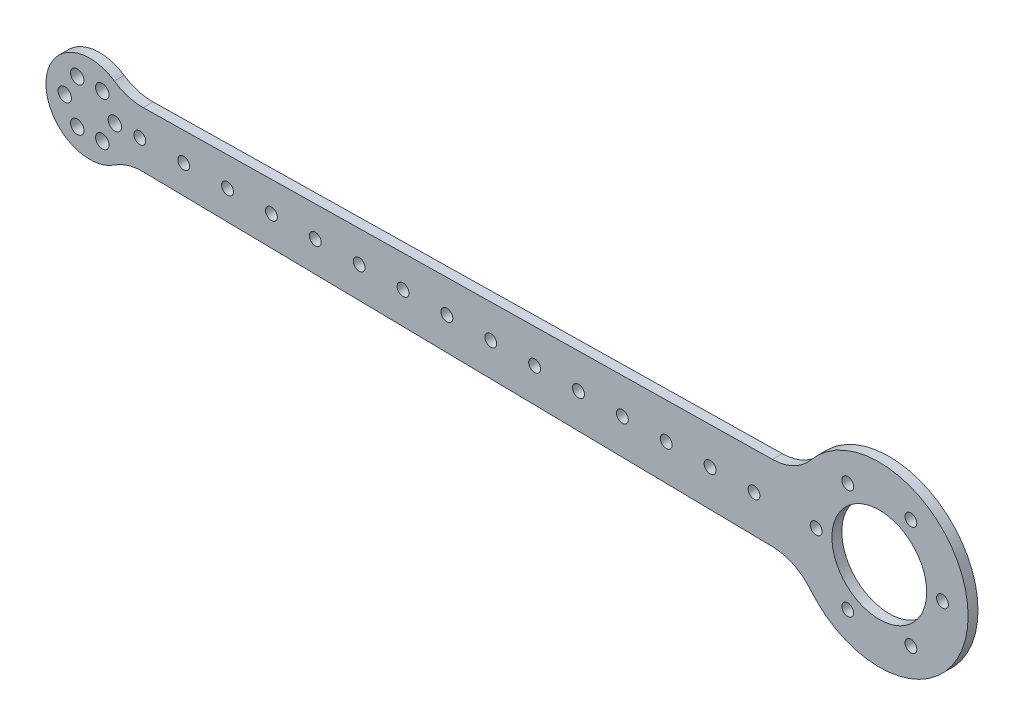
SolidWorks part; units mm, degrees
material "Hexcel AS4C (3000 Filaments)"
ref_plane "Front Plane" through (0, 0, 0) normal (0, 0, 1) x (1, 0, 0)
ref_plane "Top Plane" through (0, 0, 0) normal (0, 1, 0) x (1, 0, 0)
ref_plane "Right Plane" through (0, 0, 0) normal (1, 0, 0) x (0, 0, -1)
sketch "Sketch1" plane through (0, 0, 0) normal (0, 0, 1) x (1, 0, 0)
  line L0 (-100, 0) -> (100, 0) construction
  line L1 (-88.9892, 1.5) -> (77.8859, 4.1495)
  line L2 (-91.3398, 6.9634) -> (79.6881, 9.6788)
  line L3 (-88.9892, -1.5) -> (77.8859, -4.1495)
  line L4 (-91.3398, -6.9634) -> (79.6881, -9.6788)
  line L5 (-100, 0) -> (-100.1083, -6.8242) construction
  line L6 (-100.1083, -6.8242) -> (-91.3398, -6.9634) construction
  line L7 (-91.3398, 6.9634) -> (-100.1083, 6.8242) construction
  line L8 (-100.1083, 6.8242) -> (-100, 0) construction
  line L9 (-88.9892, 1.5) -> (-88.9892, -1.5)
  line L10 (100, 0) -> (99.8413, -9.9987) construction
  line L11 (99.8413, -9.9987) -> (79.6881, -9.6788) construction
  line L12 (79.6881, 9.6788) -> (99.8413, 9.9987) construction
  line L13 (99.8413, 9.9987) -> (100, 0) construction
  circle A0 centre (-100, 0) radius 11.1125 construction
  circle A1 centre (100, 0) radius 22.5 construction
  arc A2 (79.6881, 9.6788) -> (79.6881, -9.6788) centre (100, 0) cw
  arc A3 (77.8859, 4.1495) -> (77.8859, -4.1495) centre (100, 0) ccw
  arc A4 (-91.3398, 6.9634) -> (-91.3398, -6.9634) centre (-100, 0) ccw
  point P4 (0, 0)
  point P23 (-88.9892, 0)
  dimension "D2" = 22.225
  dimension "D3" = 45
  dimension "D1" = 200
  dimension "D5" = 5.5
  dimension "D6" = 10
  dimension "D7" = 5.5
  dimension "D4" = 10
  dimension "D8" = 3
extrude "Boss-Extrude1" add sketch "Sketch1" along normal mid plane 2.5
fillet "Fillet1" radius 12.7 4 edges at (79.6881, 9.6788, 0) (79.6881, -9.6788, 0) (-91.3398, -6.9634, 0) (-91.3398, 6.9634, 0)
sketch "Sketch2" plane through (0, 0, 0) normal (0, 0, 1) x (1, 0, 0)
  line L8 (-88.9892, 1.5) -> (-88.9892, -1.5) construction
  line L9 (-88.9892, -1.5) -> (77.8859, -4.1495) construction
  line L10 (77.8859, 4.1495) -> (-88.9892, 1.5) construction
  line L12 (-88.9892, 1.5) -> (-88.9892, -1.5)
  line L13 (-88.9892, -1.5) -> (77.8859, -4.1495)
  line L14 (77.8859, 4.1495) -> (-88.9892, 1.5)
  arc A6 (77.8859, 4.1495) -> (77.8859, -4.1495) centre (100, 0) ccw construction
  arc A7 (77.8859, 4.1495) -> (77.8859, -4.1495) centre (100, 0) ccw
extrude "Boss-Extrude2" add sketch "Sketch2" along normal mid plane 2.5
ref_axis "Axis1" through (100, 0, 1.25) along (0, 0, -1)
ref_axis "Axis2" through (-100, 0, 1.25) along (0, 0, -1)
sketch "Sketch3" plane through (0, 0, 0) normal (0, 0, 1) x (1, 0, 0)
  circle A0 centre (100, 0) radius 12
  dimension "D1" = 24
extrude "Cut-Extrude1" cut sketch "Sketch3" against normal through all both and the other way through all
sketch "Sketch5" plane through (0, 0, 0) normal (0, 0, 1) x (1, 0, 0)
  line L0 (100, 0) -> (116, 0) construction
  circle A0 centre (116, 0) radius 1.5
  dimension "D2" = 3
  dimension "D1" = 16
extrude "Cut-Extrude2" cut sketch "Sketch5" against normal through all both and the other way through all
pattern_circular "CirPattern1" count 6 over 360 about axis through (100, 0, 1.25) along (0, 0, -1) of "Cut-Extrude2"
sketch "Sketch6" plane through (0, 0, 1.25) normal (0, 0, 1) x (1, 0, 0)
  line L0 (100, 0) -> (68.25, 0) construction
  line L1 (-100, 0) -> (-31.7625, 0) construction
  circle A0 centre (68.25, 0) radius 1.5
  circle A1 centre (57.1375, 0) radius 1.5
  circle A2 centre (46.025, 0) radius 1.5
  circle A3 centre (34.9125, 0) radius 1.5
  circle A4 centre (23.8, 0) radius 1.5
  circle A5 centre (12.6875, 0) radius 1.5
  circle A6 centre (1.575, 0) radius 1.5
  circle A7 centre (-9.5375, 0) radius 1.5
  circle A8 centre (-20.65, 0) radius 1.5
  circle A9 centre (-31.7625, 0) radius 1.5
  circle A10 centre (-42.875, 0) radius 1.5
  circle A11 centre (-53.9875, 0) radius 1.5
  circle A12 centre (-65.1, 0) radius 1.5
  circle A13 centre (-76.2125, 0) radius 1.5
  circle A14 centre (-87.325, 0) radius 1.5
  dimension "D1" = 3
  dimension "D2" = 31.75
  dimension "D4" = 11.1125
  dimension "D3" = 15
extrude "Cut-Extrude3" cut sketch "Sketch6" against normal through all both and the other way through all
sketch "Sketch8" plane through (0, 0, 0) normal (0, 0, 1) x (1, 0, 0)
  line L1 (-115, -25.4) -> (-85, -25.4)
  line L2 (-115, -25.4) -> (-115, 25.4)
  line L3 (-115, 25.4) -> (-85, 25.4)
  line L4 (-85, -25.4) -> (-85, 25.4)
  line L5 (-115, -25.4) -> (-85, 25.4) construction
  line L6 (-115, 25.4) -> (-85, -25.4) construction
  point P0 (-100, 0)
  dimension "D1" = 15
  dimension "D2" = 50.8
extrude "Cut-Extrude4" [suppressed] cut sketch "Sketch8" against normal through all both and the other way through all
fillet "Fillet2" [suppressed] radius 2.3813
sketch "Sketch10" [suppressed] plane through (0, 0, 1.25) normal (0, 0, 1) x (1, 0, 0)
  line L0 (-100, 0) -> (-81.825, 0) construction
  line L1 (-85, -4.7688) -> (-85, 4.7688) construction
  line L2 (-81.825, -4) -> (-69.125, -4) construction
  line L3 (-81.825, -4) -> (-81.825, 4) construction
  line L4 (-81.825, 4) -> (-69.125, 4) construction
  line L5 (-69.125, -4) -> (-69.125, 4) construction
  circle A0 centre (-81.825, 4) radius 1.5
  circle A1 centre (-69.125, 4) radius 1.5
  circle A2 centre (-69.125, -4) radius 1.5
  circle A3 centre (-81.825, -4) radius 1.5
  point P8 (-81.825, 0)
  dimension "D4" = 3
  dimension "D1" = 3.175
  dimension "D2" = 12.7
  dimension "D3" = 8
extrude "Cut-Extrude5" [suppressed] cut sketch "Sketch10" against normal through all both and the other way through all
sketch "Sketch11" plane through (0, 0, 0) normal (0, 0, -1) x (-1, 0, 0)
  line L0 (93.65, 0) -> (100, 0) construction
  point P4 (93.65, 0)
  dimension "D2" = 6.35
hole_wizard "M3 Clearance Hole1" positions "Sketch12" profile "Sketch13" hole size "M3" standard "ANSI Metric" end condition up to next
sketch "Sketch12" plane through (0, 0, -1.25) normal (0, 0, -1) x (-1, 0, 0)
  point P0 (93.65, 0)
sketch "Sketch13" plane through (-93.65, 0, -1.25) normal (1, 0, 0) x (0, 1, 0)
  line L0 (0, 0) -> (0, 2.501)
  line L1 (0, 2.501) -> (1.7, 2.501)
  line L2 (1.7, 2.501) -> (1.7, 0)
  line L5 (1.7, 0) -> (0, 0)
  line L11 (0, -6.35) -> (0, 107.95) construction
  dimension "Thru Hole Dia." = 3.4
  dimension "Thru Hole Depth" = 2.501
pattern_circular "CirPattern3" count 6 over 360 about axis through (-100, 0, 1.25) along (0, 0, -1) of "M3 Clearance Hole1" reverse direction yes
equation "\"length\"= 200mm"
equation "\"D1@Sketch1\"=\"length\""
equation "\"Flange_Pulle\"= 45mm"
equation "\"D3@Sketch1\"=\"Flange_Pulle\""
equation "\"C_Upper\"= 10mm"
equation "\"Upper_Thickness\"= 5.5mm"
equation "\"D5@Sketch1\"=\"Upper_Thickness\""
equation "\"C_Lower\"= 10mm"
equation "\"D6@Sketch1\"=\"C_Lower\""
equation "\"Lower_Thickness\"= 5.5mm"
equation "\"D7@Sketch1\"=\"Lower_Thickness\""
equation "\"Foot_Diameter\"=0.875"
equation "\"D2@Sketch1\"=\"Foot_Diameter\""
equation "\"Thicknes\"= 2.5mm"
equation "\"D1@Boss-Extrude1\"=\"Thicknes\""
equation "\"D1@Boss-Extrude2\"=\"Thicknes\""
equation "\"D4@Sketch1\"=\"C_Upper\""
equation "\"m3_clearance\"= 3mm"
equation "\"screw_center_offset\"= 16mm"
equation "\"D2@Sketch5\"=\"m3_clearance\""
equation "\"D1@Sketch5\"=\"screw_center_offset\""
equation "\"D1@Sketch6\"=\"m3_clearance\""
equation "\"I_center_hole_spacing\"=0.4375"
equation "\"D4@Sketch6\"=\"I_center_hole_spacing\""
